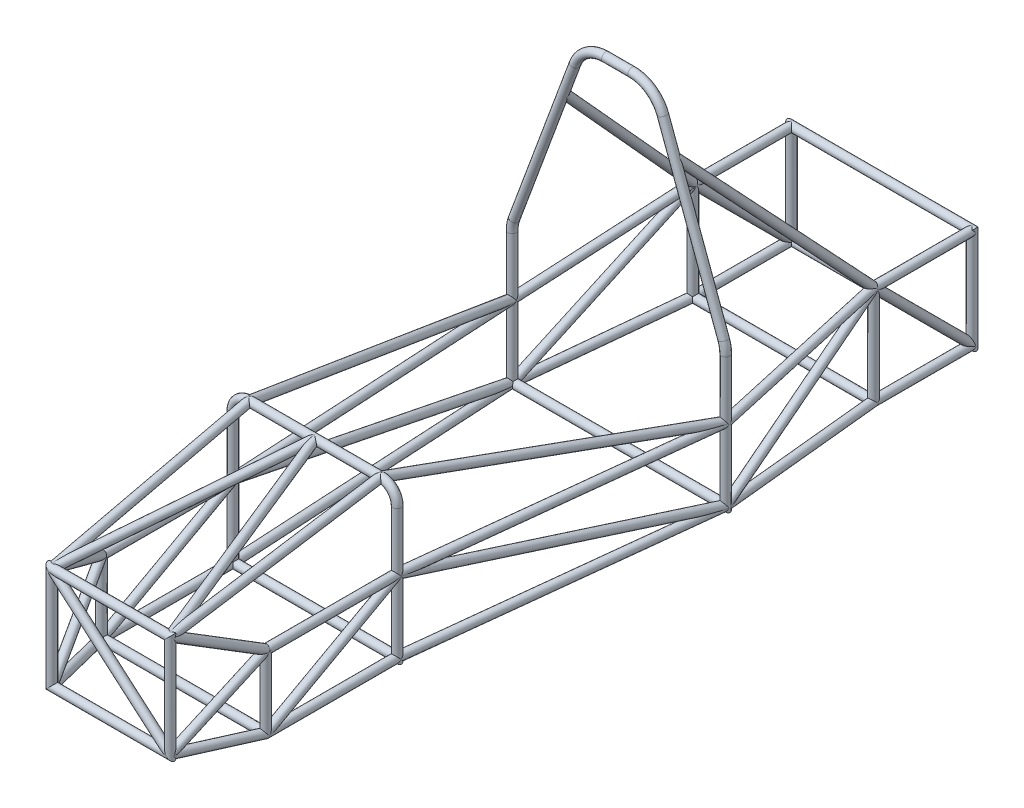
SolidWorks part; units mm, degrees
ref_plane "Front Plane" through (0, 0, 0) normal (0, 0, 1) x (1, 0, 0)
ref_plane "Top Plane" through (0, 0, 0) normal (0, 1, 0) x (1, 0, 0)
ref_plane "Right Plane" through (0, 0, 0) normal (1, 0, 0) x (0, 0, -1)
sketch "Sketch1" plane through (0, 0, 0) normal (0, 0, 1) x (1, 0, 0)
  line L0 (0, 0) -> (0, 400)
  line L1 (6.2138, 434.7009) -> (191.2138, 934.7009)
  line L2 (285, 1000) -> (365, 1000)
  line L3 (458.7862, 934.7009) -> (643.7862, 434.7009)
  line L4 (650, 400) -> (650, 0)
  line L5 (650, 0) -> (0, 0)
  line L6 (325, -975.9464) -> (325, 49024.0536) construction
  arc A0 (643.7862, 434.7009) -> (650, 400) centre (550, 400) cw
  arc A1 (0, 400) -> (6.2138, 434.7009) centre (100, 400) cw
  arc A2 (365, 1000) -> (458.7862, 934.7009) centre (365, 900) cw
  arc A3 (191.2138, 934.7009) -> (285, 1000) centre (285, 900) cw
  dimension "D2" = 100
  dimension "D3" = 100
  dimension "D1" = 650
  dimension "D4" = 325
  dimension "D5" = 400
  dimension "D6" = 80
  dimension "D7" = 1000
sketch "Sketch3" plane through (0, 0, 0) normal (0, 1, 0) x (1, 0, 0)
  line L0 (300, -1107.0637) -> (300, 51069.4933) construction
  dimension "D1" = 300
sketch3d "3DSketch26"
  line L0 (0, 0, 0) -> (50, 0, -500)
  line L2 (600, 0, -500) -> (650, 0, 0)
  line L3 (600, 0, -500) -> (50, 0, -500)
  line L4 (650, 0, 0) -> (0, 0, 0) construction
  dimension "D1" = 550
  dimension "D2" = 500
sketch3d "3DSketch30"
  line L0 (50, 0, -500) -> (50, 300, -500)
  line L2 (600, 300, -500) -> (600, 0, -500)
  dimension "D1" = 300
sketch3d "3DSketch33"
  line L0 (50, 0, -500) -> (50, 0, -800)
  line L1 (50, 0, -800) -> (600, 0, -800)
  line L2 (600, 0, -800) -> (600, 0, -500)
  line L3 (600, 0, -500) -> (50, 0, -500) construction
  dimension "D1" = 300
sketch3d "3DSketch34"
  line L0 (50, 0, -800) -> (50, 300, -800)
  line L1 (50, 300, -800) -> (600, 300, -800)
  line L2 (600, 300, -800) -> (600, 0, -800)
  dimension "D1" = 300
sketch3d "3DSketch35"
  line L0 (50, 300, -500) -> (50, 300, -800)
  line L1 (50, 300, -500) -> (50, 0, -800)
  line L2 (600, 300, -500) -> (600, 300, -800)
  line L3 (600, 300, -500) -> (600, 0, -800)
sketch3d "3DSketch36"
  line L0 (650, 0, 0) -> (600, 300, -500)
  line L1 (0, 0, 0) -> (50, 300, -500)
ref_plane "Plane1" through (0, 0, 900) normal (0, 0, 1) x (1, 0, 0)
sketch "Sketch5" plane through (0, 0, 900) normal (0, 0, 1) x (1, 0, 0)
  line L0 (50, 0) -> (550, 0)
  line L1 (650, 0) -> (0, 0) construction
  line L2 (550, 0) -> (550, 400)
  line L3 (500, 450) -> (100, 450)
  line L4 (50, 400) -> (50, 0)
  arc A0 (550, 400) -> (500, 450) centre (500, 400) ccw
  arc A1 (100, 450) -> (50, 400) centre (100, 400) ccw
  dimension "D1" = 50
  dimension "D2" = 450
  dimension "D3" = 500
  dimension "D4" = 50
sketch3d "3DSketch42"
  line L0 (0, 0, 0) -> (50, 0, 900)
  line L1 (650, 0, 0) -> (550, 0, 900)
sketch3d "3DSketch43"
  line L0 (650, 220, 0) -> (550, 220, 900)
  line L1 (650, 400, 0) -> (650, 0, 0) construction
  line L2 (550, 0, 900) -> (550, 400, 900) construction
  line L3 (550, 220, 900) -> (650, 0, 0)
  line L4 (0, 220, 0) -> (50, 220, 900)
  line L5 (0, 0, 0) -> (0, 400, 0) construction
  line L6 (50, 400, 900) -> (50, 0, 900) construction
  line L7 (50, 220, 900) -> (0, 0, 0)
  dimension "D1" = 220
  dimension "D2" = 220
  dimension "D3" = 220
  dimension "D4" = 220
sketch3d "3DSketch44"
  line L0 (650, 220, 0) -> (500, 450, 900)
  line L1 (0, 220, 0) -> (100, 450, 900)
sketch3d "3DSketch45"
  line L0 (650, 220, 0) -> (600, 300, -500)
  line L1 (0, 220, 0) -> (50, 300, -500)
sketch3d "3DSketch46"
  line L0 (50, 0, 900) -> (50, 0, 1300)
  line L1 (50, 0, 1300) -> (550, 0, 1300)
  line L2 (550, 0, 1300) -> (550, 0, 900)
  dimension "D1" = 400
sketch3d "3DSketch48"
  line L0 (50, 0, 1300) -> (50, 220, 1300)
  line L1 (50, 220, 1300) -> (50, 220, 900)
  line L2 (50, 400, 900) -> (50, 0, 900) construction
  line L3 (50, 0, 1300) -> (50, 220, 900)
  line L4 (550, 0, 1300) -> (550, 220, 1300)
  line L5 (550, 220, 1300) -> (550, 220, 900)
  line L6 (550, 0, 900) -> (550, 400, 900) construction
  line L7 (550, 220, 900) -> (550, 0, 1300)
  dimension "D1" = 220
ref_plane "Plane2" through (0, 0, 1550) normal (0, 0, 1) x (1, 0, 0)
sketch "Sketch6" plane through (0, 0, 1550) normal (0, 0, 1) x (1, 0, 0)
  line L0 (149, 49) -> (509, 49)
  line L1 (509, 49) -> (509, 359)
  line L2 (509, 359) -> (149, 359)
  line L3 (149, 359) -> (149, 49)
  line L4 (0, 0) -> (0, 400) construction
  line L5 (650, 0) -> (0, 0) construction
  dimension "D1" = 360
  dimension "D2" = 310
  dimension "D3" = 149
  dimension "D4" = 49
sketch3d "3DSketch49"
  line L0 (50, 0, 1300) -> (149, 49, 1550)
  line L1 (149, 49, 1550) -> (50, 220, 1300)
  line L2 (50, 220, 1300) -> (149, 359, 1550)
  line L3 (509, 359, 1550) -> (500, 450, 900)
  line L5 (149, 359, 1550) -> (100, 450, 900)
  line L6 (509, 359, 1550) -> (550, 220, 1300)
  line L7 (550, 220, 1300) -> (509, 49, 1550)
  line L8 (509, 49, 1550) -> (509, 359, 1550) construction
  line L9 (149, 49, 1550) -> (509, 49, 1550) construction
  line L10 (509, 49, 1550) -> (550, 0, 1300)
  line L11 (509, 359, 1550) -> (300, 450, 900)
  line L12 (149, 359, 1550) -> (509, 49, 1550)
  line L14 (500, 450, 900) -> (100, 450, 900) construction
  line L15 (300, 450, 900) -> (149, 359, 1550)
sketch "Sketch7" plane through (0, 0, 0) normal (1, 0, 0) x (0, 0, -1)
  line L0 (-592.8118, 105.9189) -> (-1507.8118, 105.9189) construction
  line L1 (-592.8118, 105.9189) -> (-180, 369.9008) construction
  line L2 (-180, 369.9008) -> (-180, 649.9008) construction
  line L5 (-900, 450) -> (0, 1009.3878) construction
  line L6 (0, 1000) -> (0, 934.7009) construction
  line L7 (0, -200975.9464) -> (0, 249024.0536) construction
  line L8 (0, 1009.3878) -> (500, 300) construction
  circle A0 centre (-592.8118, 105.9189) radius 100 construction
  arc A1 (-1488.4845, -81.1513) -> (-1432.7087, 468.959) centre (-592.8118, 105.9189) cw construction
  circle A2 centre (-180, 369.9008) radius 100 construction
  circle A3 centre (-180, 649.9008) radius 150 construction
  dimension "D1" = 200
  dimension "D2" = 915
  dimension "D4" = 490
  dimension "D3" = 180
  dimension "D5" = 280
sketch3d "3DSketch51"
  line L0 (50, 300, -500) -> (156.1745, 840, 0)
  line L1 (6.2138, 434.7009, 0) -> (191.2138, 934.7009, 0) construction
  line L2 (600, 300, -500) -> (493.8255, 840, 0)
  line L3 (458.7862, 934.7009, 0) -> (643.7862, 434.7009, 0) construction
  line L4 (285, 1000, 0) -> (365, 1000, 0) construction
  dimension "D1" = 160
sketch3d "3DSketch52"
  line L0 (0, 649.9008, 180) -> (325, 649.9008, 180) construction
  circle A0 centre (325, 649.9008, 180) radius 150 construction
  point P4 (325, 649.9008, 330)
  point P5 (0, 0, 0)
  dimension "D1" = 325
ref_plane "Plane3" through (650, 400, 0) normal (0, -1, 0) x (1, 0, 0)
ref_plane "Plane4" through (643.7862, 434.7009, 0) normal (0.347, -0.9379, 0) x (0.9379, 0.347, 0)
ref_plane "Plane5" through (458.7862, 934.7009, 0) normal (0.347, -0.9379, 0) x (0.9379, 0.347, 0)
ref_plane "Plane6" through (650, 400, 0) normal (0, -1, 0) x (1, 0, 0)
ref_plane "Plane7" through (650, 0, 0) normal (-0.1104, 0, 0.9939) x (0.9939, 0, 0.1104)
ref_plane "Plane8" through (650, 220, 0) normal (-0.1594, 0.2444, 0.9565) x (0.9871, 0.0264, 0.1578)
ref_plane "Plane9" through (650, 220, 0) normal (-0.1594, 0.2444, 0.9565) x (0.9871, 0.0264, 0.1578)
ref_plane "Plane11" through (650, 0, 0) normal (-0.1104, 0, 0.9939) x (0.9939, 0, 0.1104)
ref_plane "Plane12" through (650, 400, 0) normal (0, -1, 0) x (1, 0, 0)
ref_plane "Plane13" through (149, 359, 1550) normal (0.7578, -0.6525, 0) x (0.4258, 0.4945, -0.7578)
ref_plane "Plane14" through (650, 400, 0) normal (0, -1, 0) x (1, 0, 0)
other "Pipe MAIN HOOP(1)" corner treatment miter
ref_plane "Plane15" through (650, 400, 0) normal (0, -1, 0) x (1, 0, 0)
sketch "Sketch13" plane through (650, 400, 0) normal (0, -1, 0) x (1, 0, 0)
  circle A0 centre (0, 0) radius 12.7
  circle A1 centre (0, 0) radius 10.3
  point P4 (0, 0)
  dimension "D1" = 25.4
  dimension "D2" = 2.4
other "Pipe MAIN HOOP(2)" corner treatment miter
ref_plane "Plane16" through (550, 0, 900) normal (0, 1, 0) x (-1, 0, 0)
sketch "Sketch14" plane through (550, 0, 900) normal (0, 1, 0) x (-1, 0, 0)
  circle A0 centre (0, 0) radius 12.7
  circle A1 centre (0, 0) radius 10.3
  point P4 (0, 0)
  dimension "D1" = 25.4
  dimension "D2" = 2.4
other "Pipe SECONDARY PROFILE(1)" corner treatment miter
ref_plane "Plane17" through (509, 49, 1550) normal (0, 1, 0) x (-1, 0, 0)
sketch "Sketch16" plane through (509, 49, 1550) normal (0, 1, 0) x (-1, 0, 0)
  circle A0 centre (0, 0) radius 12.7
  circle A1 centre (0, 0) radius 11.05
  point P4 (0, 0)
  dimension "D1" = 25.4
  dimension "D2" = 1.65
other "Pipe SECONDARY PROFILE(2)" corner treatment miter
ref_plane "Plane18" through (650, 220, 0) normal (-0.1104, 0, 0.9939) x (0.9939, 0, 0.1104)
sketch "Sketch17" plane through (650, 220, 0) normal (-0.1104, 0, 0.9939) x (0.9939, 0, 0.1104)
  circle A0 centre (0, 0) radius 12.7
  circle A1 centre (0, 0) radius 11.05
  point P4 (0, 0)
  dimension "D1" = 25.4
  dimension "D2" = 1.65
other "Pipe SECONDARY PROFILE(3)" corner treatment miter
ref_plane "Plane19" through (550, 220, 900) normal (0.1073, -0.2361, -0.9658) x (0.6634, 0.7405, -0.1073)
sketch "Sketch18" plane through (550, 220, 900) normal (0.1073, -0.2361, -0.9658) x (0.6634, 0.7405, -0.1073)
  circle A0 centre (0, 0) radius 12.7
  circle A1 centre (0, 0) radius 11.05
  point P4 (0, 0)
  dimension "D1" = 25.4
  dimension "D2" = 1.65
other "Pipe SECONDARY PROFILE(4)" corner treatment miter
ref_plane "Plane20" through (0, 0, 0) normal (0.0555, 0, 0.9985) x (0.9985, 0, -0.0555)
sketch "Sketch19" plane through (0, 0, 0) normal (0.0555, 0, 0.9985) x (0.9985, 0, -0.0555)
  circle A0 centre (0, 0) radius 12.7
  circle A1 centre (0, 0) radius 11.05
  point P4 (0, 0)
  dimension "D1" = 25.4
  dimension "D2" = 1.65
other "Pipe SECONDARY PROFILE(5)" corner treatment miter
ref_plane "Plane21" through (50, 220, 900) normal (-0.0539, -0.2371, -0.97) x (0.9032, -0.4257, 0.0539)
sketch "Sketch110" plane through (50, 220, 900) normal (-0.0539, -0.2371, -0.97) x (0.9032, -0.4257, 0.0539)
  circle A0 centre (0, 0) radius 12.7
  circle A1 centre (0, 0) radius 11.05
  point P4 (0, 0)
  dimension "D1" = 25.4
  dimension "D2" = 1.65
other "Pipe TERTIARY PROFILE(1)"
ref_plane "Plane22" through (509, 359, 1550) normal (-0.3034, 0.1321, -0.9437) x (-0.6339, 0.7114, 0.3034)
sketch "Sketch112" plane through (509, 359, 1550) normal (-0.3034, 0.1321, -0.9437) x (-0.6339, 0.7114, 0.3034)
  circle A0 centre (0, 0) radius 12.7
  circle A1 centre (0, 0) radius 11.5
  point P4 (0, 0)
  dimension "D1" = 25.4
  dimension "D2" = 1.2
other "Pipe SECONDARY PROFILE(6)" corner treatment miter
ref_plane "Plane23" through (509, 359, 1550) normal (-0.0137, 0.1386, -0.9902) x (0.9807, 0.1949, 0.0137)
sketch "Sketch114" plane through (509, 359, 1550) normal (-0.0137, 0.1386, -0.9902) x (0.9807, 0.1949, 0.0137)
  circle A0 centre (0, 0) radius 12.7
  circle A1 centre (0, 0) radius 11.05
  point P4 (0, 0)
  dimension "D1" = 25.4
  dimension "D2" = 1.65
other "Pipe SECONDARY PROFILE(7)" corner treatment miter
ref_plane "Plane24" through (149, 359, 1550) normal (-0.0744, 0.1383, -0.9876) x (0.5532, 0.8297, 0.0744)
sketch "Sketch115" plane through (149, 359, 1550) normal (-0.0744, 0.1383, -0.9876) x (0.5532, 0.8297, 0.0744)
  circle A0 centre (0, 0) radius 12.7
  circle A1 centre (0, 0) radius 11.05
  point P4 (0, 0)
  dimension "D1" = 25.4
  dimension "D2" = 1.65
other "Pipe SECONDARY PROFILE(8)" corner treatment miter
ref_plane "Plane25" through (509, 49, 1550) normal (0.1589, -0.1899, -0.9689) x (0.1892, 0.969, -0.1589)
sketch "Sketch116" plane through (509, 49, 1550) normal (0.1589, -0.1899, -0.9689) x (0.1892, 0.969, -0.1589)
  circle A0 centre (0, 0) radius 12.7
  circle A1 centre (0, 0) radius 11.05
  point P4 (0, 0)
  dimension "D1" = 25.4
  dimension "D2" = 1.65
other "Pipe SECONDARY PROFILE(10)" corner treatment miter
ref_plane "Plane26" through (50, 0, 1300) normal (0.3622, 0.1793, 0.9147) x (0.9315, -0.0339, -0.3622)
sketch "Sketch117" plane through (50, 0, 1300) normal (0.3622, 0.1793, 0.9147) x (0.9315, -0.0339, -0.3622)
  circle A0 centre (0, 0) radius 12.7
  circle A1 centre (0, 0) radius 11.05
  point P4 (0, 0)
  dimension "D1" = 25.4
  dimension "D2" = 1.65
other "Pipe SECONDARY PROFILE(11)" corner treatment miter
ref_plane "Plane27" through (149, 49, 1550) normal (-0.3107, 0.5366, -0.7845) x (0.552, 0.7738, 0.3107)
sketch "Sketch118" plane through (149, 49, 1550) normal (-0.3107, 0.5366, -0.7845) x (0.552, 0.7738, 0.3107)
  circle A0 centre (0, 0) radius 12.7
  circle A1 centre (0, 0) radius 11.05
  point P4 (0, 0)
  dimension "D1" = 25.4
  dimension "D2" = 1.65
other "Pipe SECONDARY PROFILE(12)" corner treatment miter
ref_plane "Plane28" through (550, 220, 1300) normal (-0.1341, -0.5595, 0.8179) x (0.9901, -0.0413, 0.1341)
sketch "Sketch119" plane through (550, 220, 1300) normal (-0.1341, -0.5595, 0.8179) x (0.9901, -0.0413, 0.1341)
  circle A0 centre (0, 0) radius 12.7
  circle A1 centre (0, 0) radius 11.05
  point P4 (0, 0)
  dimension "D1" = 25.4
  dimension "D2" = 1.65
other "Pipe TERTIARY PROFILE(3)" corner treatment miter
ref_plane "Plane29" through (149, 359, 1550) normal (0.7578, -0.6525, 0) x (0.4258, 0.4945, -0.7578)
sketch "Sketch121" plane through (149, 359, 1550) normal (0.7578, -0.6525, 0) x (0.4258, 0.4945, -0.7578)
  circle A0 centre (0, 0) radius 12.7
  circle A1 centre (0, 0) radius 11.5
  point P4 (0, 0)
  dimension "D1" = 25.4
  dimension "D2" = 1.2
other "Pipe SECONDARY PROFILE(14)" corner treatment miter
ref_plane "Plane31" through (50, 0, 1300) normal (1, 0, 0) x (0, 0, -1)
sketch "Sketch124" plane through (50, 0, 1300) normal (1, 0, 0) x (0, 0, -1)
  circle A0 centre (0, 0) radius 12.7
  circle A1 centre (0, 0) radius 11.05
  point P4 (0, 0)
  dimension "D1" = 25.4
  dimension "D2" = 1.65
other "Pipe TERTIARY PROFILE(4)" corner treatment miter
ref_plane "Plane32" through (550, 220, 900) normal (0, -0.4819, 0.8762) x (1, 0, 0)
sketch "Sketch126" plane through (550, 220, 900) normal (0, -0.4819, 0.8762) x (1, 0, 0)
  circle A0 centre (0, 0) radius 12.7
  circle A1 centre (0, 0) radius 11.5
  point P4 (0, 0)
  dimension "D1" = 25.4
  dimension "D2" = 1.2
other "Pipe TERTIARY PROFILE(5)" corner treatment miter
ref_plane "Plane33" through (50, 0, 1300) normal (0, 0.4819, -0.8762) x (1, 0, 0)
sketch "Sketch127" plane through (50, 0, 1300) normal (0, 0.4819, -0.8762) x (1, 0, 0)
  circle A0 centre (0, 0) radius 12.7
  circle A1 centre (0, 0) radius 11.5
  point P4 (0, 0)
  dimension "D1" = 25.4
  dimension "D2" = 1.2
other "Pipe SECONDARY PROFILE(15)" corner treatment miter
ref_plane "Plane34" through (50, 0, 1300) normal (0, 1, 0) x (1, 0, 0)
sketch "Sketch129" plane through (50, 0, 1300) normal (0, 1, 0) x (1, 0, 0)
  circle A0 centre (0, 0) radius 12.7
  circle A1 centre (0, 0) radius 11.05
  point P4 (0, 0)
  dimension "D1" = 25.4
  dimension "D2" = 1.65
other "Pipe SECONDARY PROFILE(16)" corner treatment miter
ref_plane "Plane35" through (550, 0, 1300) normal (0, 1, 0) x (1, 0, 0)
sketch "Sketch130" plane through (550, 0, 1300) normal (0, 1, 0) x (1, 0, 0)
  circle A0 centre (0, 0) radius 12.7
  circle A1 centre (0, 0) radius 11.05
  point P4 (0, 0)
  dimension "D1" = 25.4
  dimension "D2" = 1.65
other "Pipe SECONDARY PROFILE(20)" corner treatment miter
ref_plane "Plane40" through (50, 300, -800) normal (1, 0, 0) x (0, 0, -1)
sketch "Sketch135" plane through (50, 300, -800) normal (1, 0, 0) x (0, 0, -1)
  circle A0 centre (0, 0) radius 12.7
  circle A1 centre (0, 0) radius 11.05
  point P4 (0, 0)
  dimension "D1" = 25.4
  dimension "D2" = 1.65
other "Pipe SECONDARY PROFILE(21)" corner treatment miter
ref_plane "Plane41" through (600, 0, -500) normal (0.0995, 0, 0.995) x (0.995, 0, -0.0995)
sketch "Sketch136" plane through (600, 0, -500) normal (0.0995, 0, 0.995) x (0.995, 0, -0.0995)
  circle A0 centre (0, 0) radius 12.7
  circle A1 centre (0, 0) radius 11.05
  point P4 (0, 0)
  dimension "D1" = 25.4
  dimension "D2" = 1.65
other "Pipe SECONDARY PROFILE(22)" corner treatment miter
ref_plane "Plane42" through (0, 0, 0) normal (0.0995, 0, -0.995) x (-0.995, 0, -0.0995)
sketch "Sketch137" plane through (0, 0, 0) normal (0.0995, 0, -0.995) x (-0.995, 0, -0.0995)
  circle A0 centre (0, 0) radius 12.7
  circle A1 centre (0, 0) radius 11.05
  point P4 (0, 0)
  dimension "D1" = 25.4
  dimension "D2" = 1.65
other "Pipe SECONDARY PROFILE(23)" corner treatment miter
ref_plane "Plane43" through (650, 220, 0) normal (-0.0983, 0.1572, -0.9827) x (0.4431, 0.8911, 0.0983)
sketch "Sketch138" plane through (650, 220, 0) normal (-0.0983, 0.1572, -0.9827) x (0.4431, 0.8911, 0.0983)
  circle A0 centre (0, 0) radius 12.7
  circle A1 centre (0, 0) radius 11.05
  point P4 (0, 0)
  dimension "D1" = 25.4
  dimension "D2" = 1.65
other "Pipe SECONDARY PROFILE(24)" corner treatment miter
ref_plane "Plane44" through (0, 220, 0) normal (0.0983, 0.1572, -0.9827) x (0.4431, -0.8911, -0.0983)
sketch "Sketch139" plane through (0, 220, 0) normal (0.0983, 0.1572, -0.9827) x (0.4431, -0.8911, -0.0983)
  circle A0 centre (0, 0) radius 12.7
  circle A1 centre (0, 0) radius 11.05
  point P4 (0, 0)
  dimension "D1" = 25.4
  dimension "D2" = 1.65
other "Pipe SECONDARY PROFILE(25)" corner treatment miter
ref_plane "Plane45" through (50, 0, -500) normal (0, 1, 0) x (1, 0, 0)
sketch "Sketch140" plane through (50, 0, -500) normal (0, 1, 0) x (1, 0, 0)
  circle A0 centre (0, 0) radius 12.7
  circle A1 centre (0, 0) radius 11.05
  point P4 (0, 0)
  dimension "D1" = 25.4
  dimension "D2" = 1.65
other "Pipe SECONDARY PROFILE(26)" corner treatment miter
ref_plane "Plane46" through (600, 300, -500) normal (0, -1, 0) x (1, 0, 0)
sketch "Sketch141" plane through (600, 300, -500) normal (0, -1, 0) x (1, 0, 0)
  circle A0 centre (0, 0) radius 12.7
  circle A1 centre (0, 0) radius 11.05
  point P4 (0, 0)
  dimension "D1" = 25.4
  dimension "D2" = 1.65
other "Pipe SECONDARY PROFILE(27)" corner treatment miter
ref_plane "Plane47" through (600, 300, -500) normal (-0.1428, 0.7262, 0.6724) x (0.9878, 0.062, 0.1428)
sketch "Sketch142" plane through (600, 300, -500) normal (-0.1428, 0.7262, 0.6724) x (0.9878, 0.062, 0.1428)
  circle A0 centre (0, 0) radius 12.7
  circle A1 centre (0, 0) radius 11.05
  point P4 (0, 0)
  dimension "D1" = 25.4
  dimension "D2" = 1.65
other "Pipe SECONDARY PROFILE(28)" corner treatment miter
ref_plane "Plane48" through (50, 300, -500) normal (0.1428, 0.7262, 0.6724) x (0.9878, -0.062, -0.1428)
sketch "Sketch143" plane through (50, 300, -500) normal (0.1428, 0.7262, 0.6724) x (0.9878, -0.062, -0.1428)
  circle A0 centre (0, 0) radius 12.7
  circle A1 centre (0, 0) radius 11.05
  point P4 (0, 0)
  dimension "D1" = 25.4
  dimension "D2" = 1.65
other "Pipe SECONDARY PROFILE(29)" corner treatment miter
ref_plane "Plane49" through (600, 0, -500) normal (-1, 0, 0) x (0, 0, 1)
sketch "Sketch144" plane through (600, 0, -500) normal (-1, 0, 0) x (0, 0, 1)
  circle A0 centre (0, 0) radius 12.7
  circle A1 centre (0, 0) radius 11.05
  point P4 (0, 0)
  dimension "D1" = 25.4
  dimension "D2" = 1.65
other "Pipe SECONDARY PROFILE(30)" corner treatment miter
ref_plane "Plane50" through (600, 300, -500) normal (0, -0.7071, -0.7071) x (1, 0, 0)
sketch "Sketch145" plane through (600, 300, -500) normal (0, -0.7071, -0.7071) x (1, 0, 0)
  circle A0 centre (0, 0) radius 12.7
  circle A1 centre (0, 0) radius 11.05
  point P4 (0, 0)
  dimension "D1" = 25.4
  dimension "D2" = 1.65
other "Pipe SECONDARY PROFILE(31)" corner treatment miter
ref_plane "Plane51" through (650, 0, 0) normal (-0.0854, 0.5126, -0.8544) x (0.9499, 0.3007, 0.0854)
sketch "Sketch146" plane through (650, 0, 0) normal (-0.0854, 0.5126, -0.8544) x (0.9499, 0.3007, 0.0854)
  circle A0 centre (0, 0) radius 12.7
  circle A1 centre (0, 0) radius 11.05
  point P4 (0, 0)
  dimension "D1" = 25.4
  dimension "D2" = 1.65
other "Pipe SECONDARY PROFILE(32)" corner treatment miter
ref_plane "Plane52" through (50, 300, -500) normal (0, -0.7071, -0.7071) x (1, 0, 0)
sketch "Sketch147" plane through (50, 300, -500) normal (0, -0.7071, -0.7071) x (1, 0, 0)
  circle A0 centre (0, 0) radius 12.7
  circle A1 centre (0, 0) radius 11.05
  point P4 (0, 0)
  dimension "D1" = 25.4
  dimension "D2" = 1.65
other "Pipe SECONDARY PROFILE(33)" corner treatment miter
ref_plane "Plane53" through (0, 0, 0) normal (0.0854, 0.5126, -0.8544) x (0.9499, -0.3007, -0.0854)
sketch "Sketch148" plane through (0, 0, 0) normal (0.0854, 0.5126, -0.8544) x (0.9499, -0.3007, -0.0854)
  circle A0 centre (0, 0) radius 12.7
  circle A1 centre (0, 0) radius 11.05
  point P4 (0, 0)
  dimension "D1" = 25.4
  dimension "D2" = 1.65
